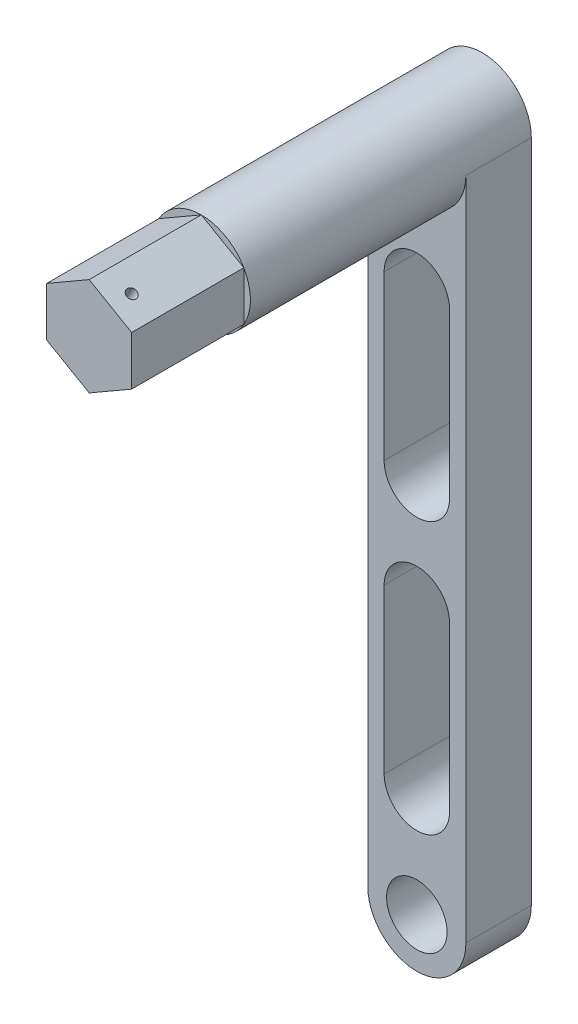
SolidWorks part; units mm, degrees
material "PEI"
ref_plane "Front Plane" through (0, 0, 0) normal (0, 0, 1) x (1, 0, 0)
ref_plane "Top Plane" through (0, 0, 0) normal (0, 1, 0) x (1, 0, 0)
ref_plane "Right Plane" through (0, 0, 0) normal (1, 0, 0) x (0, 0, -1)
sketch "Sketch1" plane through (0, 0, 0) normal (0, 0, 1) x (1, 0, 0)
  line L0 (0, -50.8) -> (0, 50.8) construction
  line L1 (-7.5, -50.8) -> (-7.5, 50.8)
  line L2 (7.5, -50.8) -> (7.5, 50.8)
  line L3 (0, -34.675) -> (0, -9.675) construction
  line L4 (-5, -34.675) -> (-5, -9.675)
  line L5 (5, -34.675) -> (5, -9.675)
  line L6 (0, 31.8) -> (0, 6.8) construction
  line L7 (5, 31.8) -> (5, 6.8)
  line L8 (-5, 31.8) -> (-5, 6.8)
  line L9 (-5, 19.3) -> (5, 19.3) construction
  line L10 (-5, -22.175) -> (5, -22.175) construction
  line L12 (0, 58.3) -> (0, 36.8) construction
  arc A0 (-7.5, -50.8) -> (7.5, -50.8) centre (0, -50.8) ccw
  arc A1 (7.5, 50.8) -> (-7.5, 50.8) centre (0, 50.8) ccw
  circle A2 centre (0, -50.8) radius 4.625
  arc A4 (-5, -34.675) -> (5, -34.675) centre (0, -34.675) ccw
  arc A5 (5, -9.675) -> (-5, -9.675) centre (0, -9.675) ccw
  arc A6 (5, 31.8) -> (-5, 31.8) centre (0, 31.8) ccw
  arc A7 (-5, 6.8) -> (5, 6.8) centre (0, 6.8) ccw
  circle A8 centre (0, 50.8) radius 7.5
  point P2 (0, 0)
  point P14 (0, -22.175)
  point P19 (0, 19.3)
  point P30 (0, -4.675)
  point P32 (0, -46.175)
  point P33 (0, -39.675)
  point P35 (0, 1.8)
  point P37 (0, 43.3)
  dimension "D3" = 9.25
  dimension "D1" = 101.6
  dimension "D2" = 15
  dimension "D4" = 10
  dimension "D5" = 6.5
  dimension "20" = 25
  dimension "D6" = 6.5
extrude "Boss-Extrude1" add sketch "Sketch1" along normal blind 10 contours A8 L1 A0 L2 A7 L8 A6 L7 A5 L5 A4 L4 A2 region at (-6.3987, 0, 0)
extrude "Boss-Extrude2" add sketch "Sketch1<4>" along normal blind 42.94 contours A1 A8 region at (0, 50.8, 0)
sketch "Sketch1<4>" plane through (0, 0, 0) normal (0, 0, 1) x (1, 0, 0) same geometry as "Sketch1"
sketch "Sketch2" plane through (0, 0, 42.94) normal (0, 0, 1) x (1, 0, 0)
  point P0 (0, 50.8)
sketch "Sketch3" plane through (0, 0, 42.94) normal (0, 0, 1) x (1, 0, 0)
  line L1 (0, 43.3) -> (6.4952, 47.05)
  line L2 (6.4952, 47.05) -> (6.4952, 54.55)
  line L3 (6.4952, 54.55) -> (0, 58.3)
  line L4 (0, 58.3) -> (-6.4952, 54.55)
  line L5 (-6.4952, 54.55) -> (-6.4952, 47.05)
  line L6 (-6.4952, 47.05) -> (0, 43.3)
  circle A0 centre (0, 50.8) radius 6.4952 construction
extrude "Boss-Extrude3" add sketch "Sketch3" along normal blind 17.14
sketch "Sketch4" plane through (25.2446, 43.725, 0) normal (0.5, 0.866, 0) x (0.866, -0.5, 0)
  line L0 (-25.4, -60.08) -> (-25.4, -56.08) construction
  line L1 (-21.65, -60.08) -> (-29.15, -60.08) construction
  circle A0 centre (-25.4, -56.83) radius 0.75
  dimension "D2" = 1.5
  dimension "D1" = 4
extrude "Cut-Extrude1" cut sketch "Sketch4" against normal through all both and the other way through all
